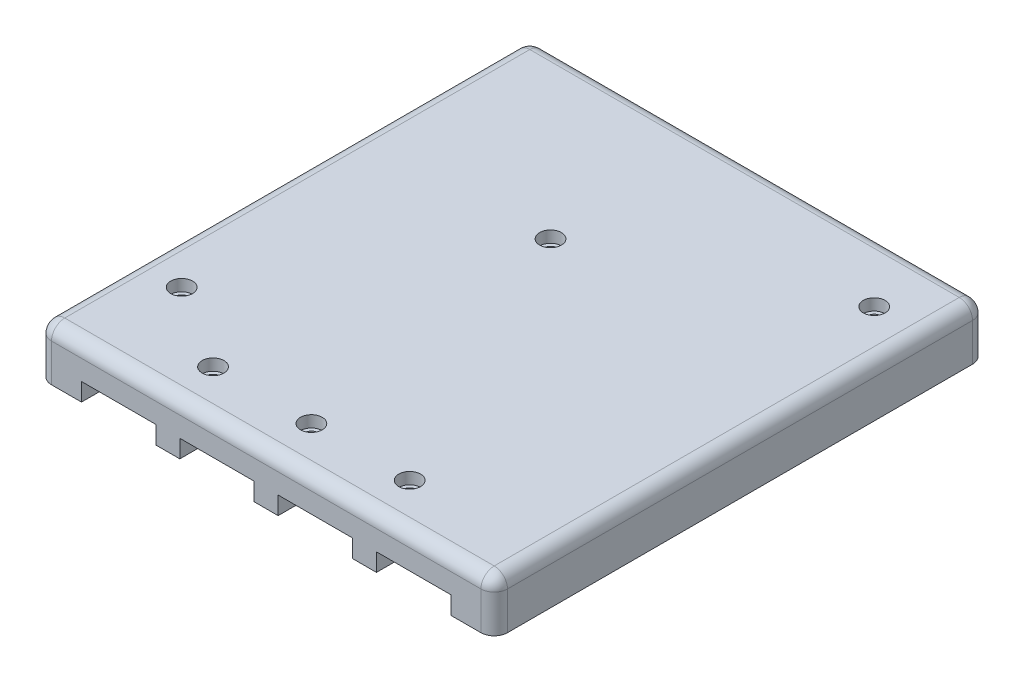
SolidWorks part; units mm, degrees
ref_plane "Front Plane" through (0, 0, 0) normal (0, 0, 1) x (1, 0, 0)
ref_plane "Top Plane" through (0, 0, 0) normal (0, 1, 0) x (1, 0, 0)
ref_plane "Right Plane" through (0, 0, 0) normal (1, 0, 0) x (0, 0, -1)
sketch "Sketch1" plane through (0, 0, 0) normal (0, 1, 0) x (1, 0, 0)
  line L0 (-1, -1) -> (-1, 15.7637) construction
  line L1 (-6, -6) -> (79.8, -6)
  line L2 (-6, -6) -> (-6, 86.5)
  line L3 (-6, 86.5) -> (79.8, 86.5)
  line L4 (79.8, -6) -> (79.8, 86.5)
  line L5 (-1, -1) -> (16.6536, -1) construction
  circle A0 centre (2.5, 12.5) radius 2.05
  circle A1 centre (18.4, 2.5) radius 2.05
  circle A2 centre (36.9, 2.5) radius 2.05
  circle A3 centre (55.4, 2.5) radius 2.05
  circle A4 centre (29.3, 55.1) radius 2.05
  circle A5 centre (70.8, 74.5) radius 2.05
  dimension "D16" = 4.1
  dimension "D1" = 92.5
  dimension "D2" = 85.8
  dimension "D3" = 5
  dimension "D4" = 1
  dimension "D5" = 1
  dimension "D6" = 5
  dimension "D7" = 12.5
  dimension "D8" = 2.5
  dimension "D9" = 18.4
  dimension "D10" = 18.5
  dimension "D11" = 18.5
  dimension "D12" = 55.1
  dimension "D13" = 29.3
  dimension "D14" = 41.5
  dimension "D15" = 74.5
  dimension "D17" = 2.5
extrude "Boss-Extrude1" add sketch "Sketch1" along normal blind 3.175
sketch "Sketch2" plane through (0, 0, 0) normal (0, 1, 0) x (1, 0, 0)
  line L0 (2.5, 7.5) -> (-1, 7.5)
  line L1 (-6, 86.5) -> (79.8, 86.5)
  line L2 (-6, 86.5) -> (-6, -6)
  line L3 (-6, -6) -> (79.8, -6)
  line L4 (79.8, 86.5) -> (79.8, -6)
  line L5 (-1, 7.5) -> (-1, -1)
  line L6 (-1, -1) -> (13.4, -1)
  line L7 (13.4, -1) -> (13.4, 2.5)
  line L8 (2.5, 17.5) -> (-1, 17.5)
  line L9 (-1, 17.5) -> (-1, 81.5)
  line L10 (-1, 81.5) -> (65.8, 81.5)
  line L11 (65.8, 74.5) -> (65.8, 81.5)
  line L13 (70.8, 69.5) -> (74.8, 69.5)
  line L14 (74.8, 69.5) -> (74.8, -1)
  line L15 (74.8, -1) -> (60.4, -1)
  line L16 (60.4, -1) -> (60.4, 2.5)
  line L17 (23.4, 2.5) -> (23.4, -1)
  line L18 (23.4, -1) -> (31.9, -1)
  line L19 (31.9, -1) -> (31.9, 2.5)
  line L20 (41.9, 2.5) -> (41.9, -1)
  line L21 (41.9, -1) -> (50.4, -1)
  line L22 (50.4, -1) -> (50.4, 2.5)
  circle A0 centre (2.5, 12.5) radius 1.35
  circle A1 centre (18.4, 2.5) radius 1.35
  circle A2 centre (36.9, 2.5) radius 1.35
  circle A3 centre (55.4, 2.5) radius 1.35
  circle A4 centre (29.3, 55.1) radius 1.35
  circle A5 centre (70.8, 74.5) radius 1.35
  circle A6 centre (29.3, 55.1) radius 3.35
  arc A7 (2.5, 17.5) -> (2.5, 7.5) centre (2.5, 12.5) cw
  arc A8 (13.4, 2.5) -> (23.4, 2.5) centre (18.4, 2.5) cw
  arc A9 (31.9, 2.5) -> (41.9, 2.5) centre (36.9, 2.5) cw
  arc A10 (50.4, 2.5) -> (60.4, 2.5) centre (55.4, 2.5) cw
  arc A11 (65.8, 74.5) -> (70.8, 69.5) centre (70.8, 74.5) ccw
  dimension "D1" = 2.7
  dimension "D2" = 6.7
  dimension "D3" = 5
  dimension "D4" = 5
  dimension "D5" = 5
  dimension "D6" = 5
  dimension "D7" = 5
extrude "Boss-Extrude2" add sketch "Sketch2" against normal blind 1.905 contours L4 L1 L2 L3 A0 A1 A2 A3 A5 L11 A11 L13 L14 L15 L16 A10 L22 L21 L20 A9 L19 L18 L17 A8 L7 L6 L5 L0 A7 L8 L9 L10 | A6 A4 region at (36.9, 0, -85.2383) region at (26.0448, 0, -55.1)
extrude "Boss-Extrude3" add sketch "Sketch2<3>" along normal blind 1 contours L4 L1 L2 L3 A0 A1 A2 A3 A5 L11 A11 L13 L14 L15 L16 A10 L22 L21 L20 A9 L19 L18 L17 A8 L7 L6 L5 L0 A7 L8 L9 L10 | A6 A4 region at (36.9, 0, -85.2383) region at (26.0448, 0, -55.1)
sketch "Sketch2<3>" plane through (0, 0, 0) normal (0, 1, 0) x (1, 0, 0) same geometry as "Sketch2"
ref_plane "Plane1" through (0, -1.905, 0) normal (0, -1, 0) x (-1, 0, 0)
sketch "Sketch3" plane through (0, -1.905, 0) normal (0, -1, 0) x (-1, 0, 0)
  line L1 (6, 86.5) -> (-79.8, 86.5)
  line L2 (6, 86.5) -> (6, -6)
  line L3 (6, -6) -> (-79.8, -6)
  line L4 (-79.8, 86.5) -> (-79.8, -6)
  line L5 (1, 81.5) -> (-74.8, 81.5)
  line L6 (1, 81.5) -> (1, -1)
  line L7 (1, -1) -> (-74.8, -1)
  line L8 (-74.8, 81.5) -> (-74.8, -1)
  dimension "D1" = 5
  dimension "D2" = 5
  dimension "D3" = 5
  dimension "D4" = 5
extrude "Boss-Extrude4" add sketch "Sketch3" along normal blind 4.55
sketch "Sketch4" plane through (0, 0, 0) normal (0, 0, 1) x (1, 0, 0)
  line L0 (79.8, -6.455) -> (-6, -6.455) construction
  line L1 (2.15, -3.095) -> (16.15, -3.095)
  line L2 (2.15, -3.095) -> (2.15, -9.845)
  line L3 (2.15, -9.845) -> (16.15, -9.845)
  line L4 (16.15, -3.095) -> (16.15, -9.845)
  line L5 (20.65, -3.095) -> (34.65, -3.095)
  line L6 (20.65, -3.095) -> (20.65, -9.845)
  line L7 (20.65, -9.845) -> (34.65, -9.845)
  line L8 (34.65, -3.095) -> (34.65, -9.845)
  line L9 (39.15, -3.095) -> (53.15, -3.095)
  line L10 (39.15, -3.095) -> (39.15, -9.845)
  line L11 (39.15, -9.845) -> (53.15, -9.845)
  line L12 (53.15, -3.095) -> (53.15, -9.845)
  line L13 (57.65, -3.095) -> (71.65, -3.095)
  line L14 (57.65, -3.095) -> (57.65, -9.845)
  line L15 (57.65, -9.845) -> (71.65, -9.845)
  line L16 (71.65, -3.095) -> (71.65, -9.845)
  point P16 (9.15, -3.095)
  point P17 (27.65, -3.095)
  point P18 (46.15, -3.095)
  point P19 (64.65, -3.095)
  dimension "D1" = 14
  dimension "D2" = 14
  dimension "D3" = 14
  dimension "D4" = 14
  dimension "D5" = 9.15
  dimension "D6" = 18.5
  dimension "D7" = 18.5
  dimension "D8" = 18.5
  dimension "D9" = 6.75
  dimension "D10" = 3.36
extrude "Cut-Extrude1" cut sketch "Sketch4" along normal through all
sketch "Sketch5" plane through (0, 0, 0) normal (0, 0, 1) x (1, 0, 0)
  line L0 (-1, -6.455) -> (74.8, -6.455) construction
  line L1 (53, -4.455) -> (63, -4.455)
  line L2 (53, -4.455) -> (53, -10.455)
  line L3 (53, -10.455) -> (63, -10.455)
  line L4 (63, -4.455) -> (63, -10.455)
  point P4 (58, -4.455)
  dimension "D1" = 58
  dimension "D2" = 10
  dimension "D3" = 6
  dimension "D4" = 2
extrude "Cut-Extrude2" cut sketch "Sketch5" against normal through all
ref_plane "Plane2" through (-6, 0, 0) normal (-1, 0, 0) x (0, 0, 1)
sketch "Sketch6" plane through (-6, 0, 0) normal (-1, 0, 0) x (0, 0, 1)
  line L0 (-59.6, 0) -> (-59.6, -8.95)
  line L1 (-59.6, 0) -> (-50.6, 0)
  line L2 (-59.6, -8.95) -> (-59.1311, -8.95)
  line L3 (-50.6, 0) -> (-50.6, -8.95)
  line L4 (-50.6, -8.95) -> (-51.0689, -8.95)
  arc A0 (-59.1311, -8.95) -> (-51.0689, -8.95) centre (-55.1, -10.95) cw
  point P3 (-55.1, 0)
  dimension "D1" = 4.5
  dimension "D2" = 10.95
  dimension "D3" = 55.1
  dimension "D4" = 9
  dimension "D5" = 2
extrude "Boss-Extrude5" add sketch "Sketch6" against normal blind 5
fillet "Fillet1" radius 2.5 1 edges at (79.8, -1.64, 6)
fillet "Fillet2" radius 2.5 1 edges at (79.8, -1.64, -86.5)
fillet "Fillet3" radius 2.5 1 edges at (-6, -1.64, -86.5)
fillet "Fillet4" radius 2.5 1 edges at (-6, -1.64, 6)
fillet "Fillet5" radius 2.5 8 edges at (79.0678, 3.175, -85.7678) (79.8, 3.175, -40.25) (79.0678, 3.175, 5.2678) (36.9, 3.175, 6) (-5.2678, 3.175, 5.2678) (-6, 3.175, -40.25) (-5.2678, 3.175, -85.7678) (36.9, 3.175, -86.5)
